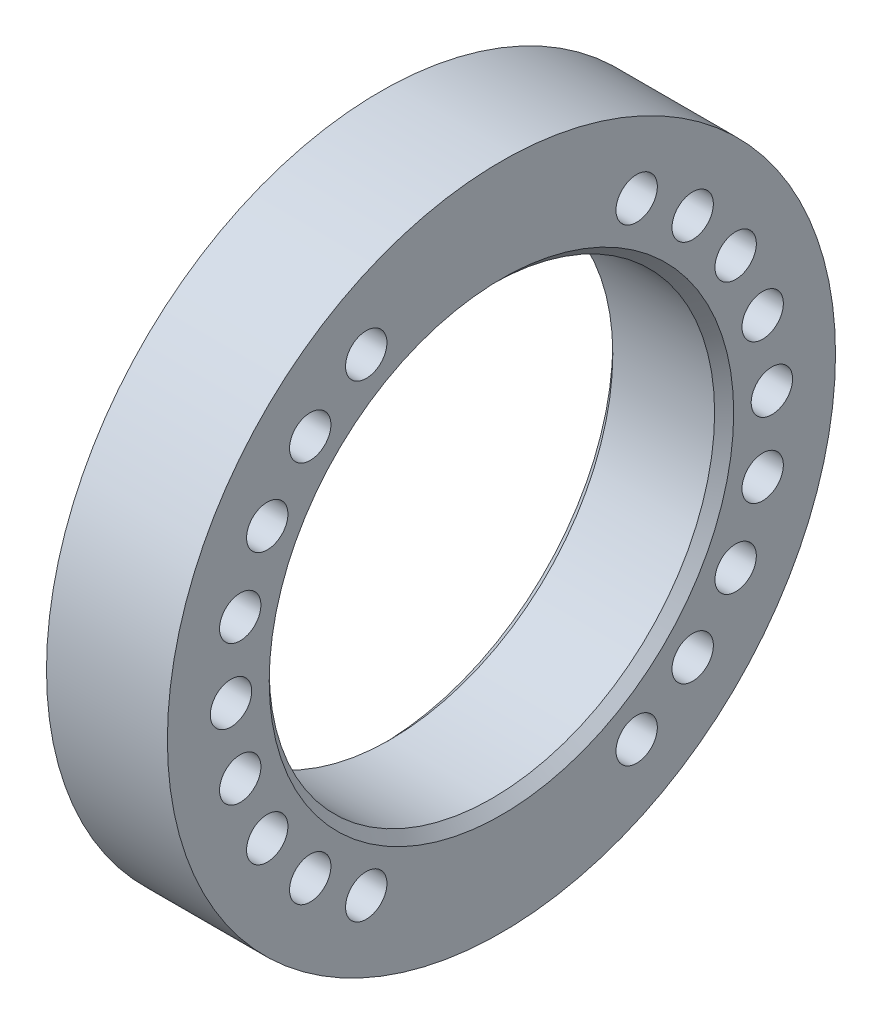
SolidWorks part; units mm, degrees
ref_plane "Front Plane" through (0, 0, 0) normal (0, 0, 1) x (1, 0, 0)
ref_plane "Top Plane" through (0, 0, 0) normal (0, 1, 0) x (1, 0, 0)
ref_plane "Right Plane" through (0, 0, 0) normal (1, 0, 0) x (0, 0, -1)
sketch "Sketch1" plane through (0, 0, 0) normal (0, 0, 1) x (1, 0, 0)
  line L0 (0, 0) -> (-74.4742, 0) construction
  line L1 (-19, 105) -> (19, 105)
  line L2 (-19, 105) -> (-19, 70)
  line L3 (-19, 70) -> (19, 70)
  line L4 (19, 105) -> (19, 70)
  line L5 (-19, 105) -> (19, 70) construction
  line L6 (-19, 70) -> (19, 105) construction
  point P0 (0, 87.5)
  dimension "D1" = 105
  dimension "D2" = 70
  dimension "D3" = 38
revolve "Revolve1" add sketch "Sketch1" angle 360 about L0
ref_axis "Axis1" through (-19, 0, 0) along (1, 0, 0)
sketch "Sketch2" plane through (19, 0, 0) normal (1, 0, 0) x (0, 0, -1)
  circle A0 centre (0, 0) radius 85 construction
  circle A1 centre (85, 0) radius 6.5
  dimension "D1" = 170
  dimension "D2" = 13
extrude "Cut-Extrude1" cut sketch "Sketch2" against normal through all
pattern_circular "CirPattern1" count 5 every 15 about axis through (-19, 0, 0) along (1, 0, 0) of "Cut-Extrude1" other way count 5
mirror "Mirror1" about plane through (0, 0, 0) normal (0, 0, 1) of "CirPattern1"
chamfer "Chamfer1" distance 3 angle 45 2 edges at (-19, 0, -70) (19, 0, -70)
